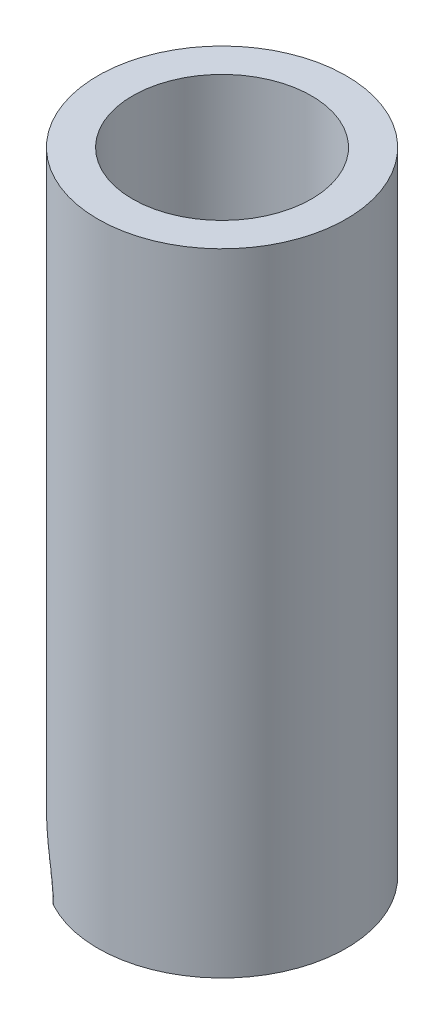
SolidWorks part; units mm, degrees
ref_plane "Front Plane" through (0, 0, 0) normal (0, 0, 1) x (1, 0, 0)
ref_plane "Top Plane" through (0, 0, 0) normal (0, 1, 0) x (1, 0, 0)
ref_plane "Right Plane" through (0, 0, 0) normal (1, 0, 0) x (0, 0, -1)
sketch "Sketch1" plane through (0, 0, 0) normal (0, 1, 0) x (1, 0, 0)
  circle A0 centre (0, 0) radius 2.95
  circle A1 centre (0, 0) radius 2.125
  dimension "D1" = 4.25
  dimension "D2" = 5.9
extrude "Boss-Extrude1" add sketch "Sketch1" along normal blind 15
sketch "Sketch2" plane through (0, 0, 0) normal (1, 0, 0) x (0, 0, -1)
  circle A0 centre (0, 0) radius 2.125
extrude "Cut-Extrude2" cut sketch "Sketch2" against normal blind 4
fillet "Fillet1" radius 0.25 2 edges at (-2.9475, 2.1215, -0.1215) (-2.125, 2.125, 0)
